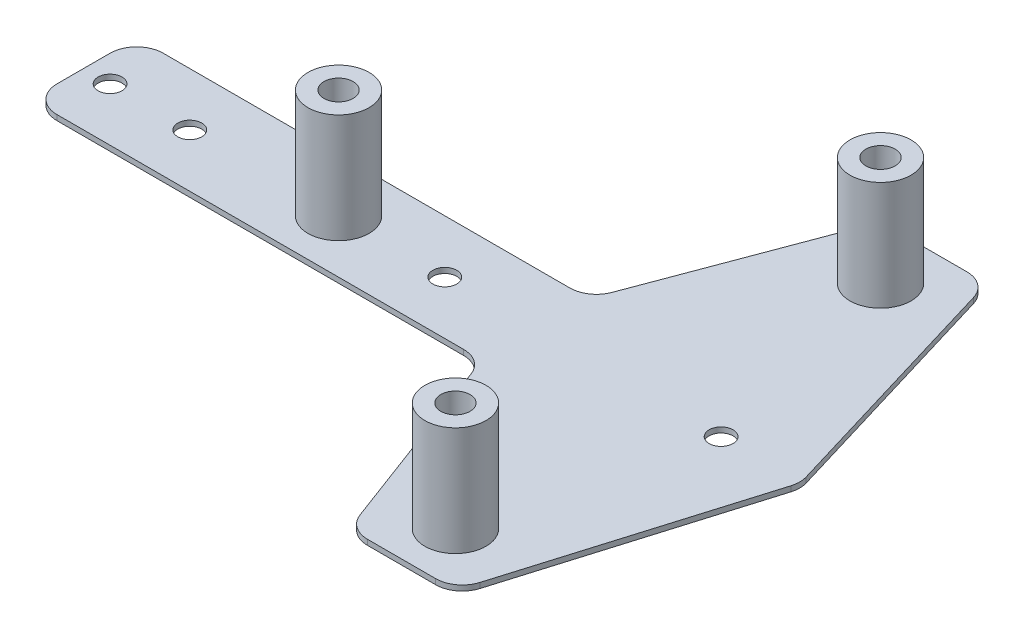
SolidWorks part; units mm, degrees
ref_plane "Front Plane" through (0, 0, 0) normal (0, 0, 1) x (1, 0, 0)
ref_plane "Top Plane" through (0, 0, 0) normal (0, 1, 0) x (1, 0, 0)
ref_plane "Right Plane" through (0, 0, 0) normal (1, 0, 0) x (0, 0, -1)
sketch "Sketch1" plane through (0, 0, 0) normal (0, 1, 0) x (1, 0, 0)
  line L0 (-55, 10) -> (6.535, 10)
  line L1 (11.2166, 13.2444) -> (23.7834, 46.7556)
  line L2 (28.465, 50) -> (41.2798, 50)
  line L3 (46.069, 46.4367) -> (59.569, 1.4367)
  line L4 (59.569, -1.4367) -> (46.069, -46.4367)
  line L5 (41.2798, -50) -> (28.465, -50)
  line L6 (23.7834, -46.7556) -> (11.2166, -13.2444)
  line L7 (6.535, -10) -> (-55, -10)
  line L8 (-60, -5) -> (-60, 5)
  line L9 (-60, 0) -> (60, 0) construction
  line L10 (10, -10) -> (10, 10) construction
  line L11 (25, 50) -> (25, -50) construction
  line L12 (45, -50) -> (45, 50) construction
  arc A0 (6.535, 10) -> (11.2166, 13.2444) centre (6.535, 15) ccw
  arc A1 (23.7834, 46.7556) -> (28.465, 50) centre (28.465, 45) cw
  arc A2 (41.2798, 50) -> (46.069, 46.4367) centre (41.2798, 45) cw
  arc A3 (59.569, 1.4367) -> (59.569, -1.4367) centre (54.7798, 0) cw
  arc A4 (46.069, -46.4367) -> (41.2798, -50) centre (41.2798, -45) cw
  arc A5 (28.465, -50) -> (23.7834, -46.7556) centre (28.465, -45) cw
  arc A6 (11.2166, -13.2444) -> (6.535, -10) centre (6.535, -15) ccw
  arc A7 (-55, -10) -> (-60, -5) centre (-55, -5) cw
  arc A8 (-55, 10) -> (-60, 5) centre (-55, 5) ccw
  point P10 (25, 0)
  point P36 (-60, -10)
  point P39 (-60, 10)
  dimension "D7" = 5
  dimension "D1" = 20
  dimension "D2" = 70
  dimension "D3" = 15
  dimension "D4" = 20
  dimension "D5" = 15
  dimension "D6" = 100
extrude "Boss-Extrude1" add sketch "Sketch1" along normal blind 1
sketch "Sketch2" plane through (0, 1, 0) normal (0, 1, 0) x (1, 0, 0)
  line L0 (-27, 0) -> (0, 0) construction
  line L1 (0, 0) -> (35, 0) construction
  line L2 (35, 40) -> (35, -40) construction
  circle A0 centre (-27, 0) radius 2.75
  circle A1 centre (35, 40) radius 2.75
  circle A2 centre (35, -40) radius 2.75
  arc A3 (59.569, -1.4367) -> (59.569, 1.4367) centre (54.7798, 0) ccw construction
  dimension "D4" = 5.5
  dimension "D1" = 62
  dimension "D2" = 19.7798
  dimension "D3" = 80
extrude "Cut-Extrude1" cut sketch "Sketch2" against normal through all
sketch "Sketch3" plane through (0, 1, 0) normal (0, 1, 0) x (1, 0, 0)
  circle A0 centre (35, -40) radius 2.75 construction
  circle A1 centre (-27, 0) radius 2.75 construction
  circle A2 centre (35, 40) radius 2.75 construction
  circle A3 centre (35, -40) radius 2.75
  circle A4 centre (-27, 0) radius 2.75
  circle A5 centre (35, 40) radius 2.75
  circle A6 centre (-27, 0) radius 5.75
  circle A7 centre (35, 40) radius 5.75
  circle A8 centre (35, -40) radius 5.75
  dimension "D1" = 3
extrude "Boss-Extrude2" add sketch "Sketch3" along normal blind 20.5
sketch "Sketch4" plane through (0, 1, 0) normal (0, 1, 0) x (1, 0, 0)
  line L0 (-55, 0) -> (0, 0) construction
  line L1 (0, 0) -> (45, 0) construction
  circle A0 centre (-55, 0) radius 2.25
  circle A1 centre (45, 0) radius 2.25
  circle A3 centre (-7, 0) radius 2.25
  arc A4 (59.569, -1.4367) -> (59.569, 1.4367) centre (54.7798, 0) ccw construction
  dimension "D2" = 4.5
  dimension "D3" = 9.7798
  dimension "D1" = 52
  dimension "D4" = 100
extrude "Cut-Extrude2" cut sketch "Sketch4" against normal through all
sketch "Sketch5" plane through (0, 0, 0) normal (0, 1, 0) x (1, 0, 0)
  line L1 (-55, 10) -> (-70, 10)
  line L2 (-55, 10) -> (-55, -10)
  line L3 (-55, -10) -> (-70, -10)
  line L4 (-75, 5) -> (-75, -5)
  line L5 (-55, -10) -> (6.535, -10) construction
  line L6 (-60, 5) -> (-60, -5) construction
  line L7 (-70, 0) -> (-55, 0) construction
  arc A0 (-70, 10) -> (-75, 5) centre (-70, 5) ccw
  arc A1 (-70, -10) -> (-75, -5) centre (-70, -5) cw
  circle A2 centre (-70, 0) radius 2.25
  circle A3 centre (-55, 0) radius 2.25 construction
  dimension "D2" = 5
  dimension "D1" = 15
  dimension "D3" = 15
extrude "Boss-Extrude3" add sketch "Sketch5" along normal up to surface (1 mm away) up to face at (-55, 1, 2.25)
sketch "Sketch6" plane through (0, 1, 0) normal (0, 1, 0) x (1, 0, 0)
  line L0 (-55, -2.25) -> (-55, 2.25) construction
  circle A0 centre (-55, 0) radius 2.25
  arc A1 (-55, -2.25) -> (-55, 2.25) centre (-55, 0) ccw construction
extrude "Cut-Extrude3" cut sketch "Sketch6" against normal through all
